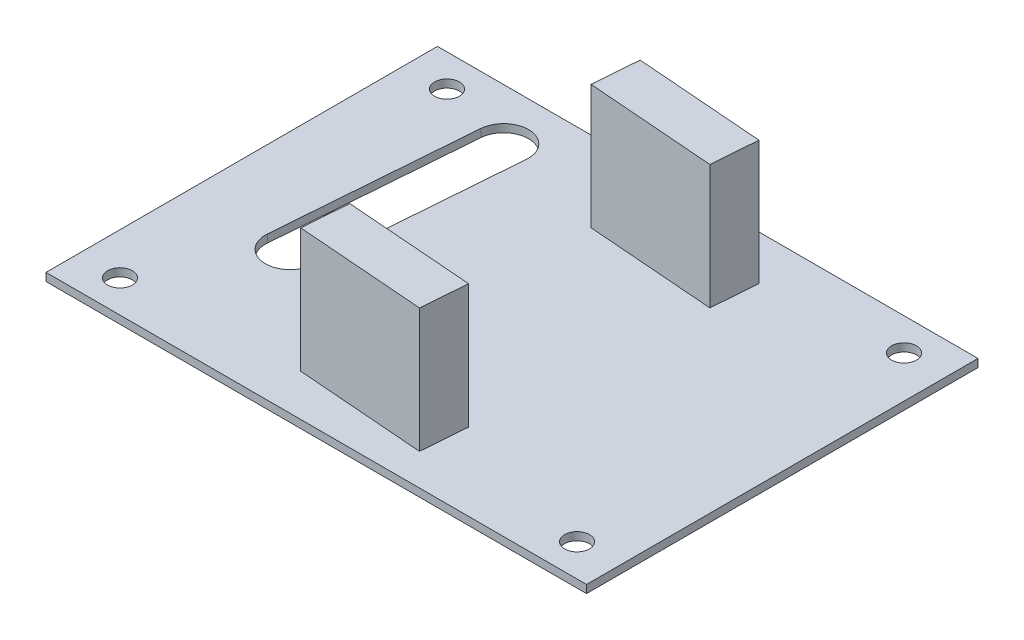
SolidWorks part; units mm, degrees
ref_plane "Ön Düzlem" through (0, 0, 0) normal (0, 0, 1) x (1, 0, 0)
ref_plane "Üst Düzlem" through (0, 0, 0) normal (0, 1, 0) x (1, 0, 0)
ref_plane "Sağ Düzlem" through (0, 0, 0) normal (1, 0, 0) x (0, 0, -1)
sketch "Çizim1" plane through (0, 0, 0) normal (0, 1, 0) x (1, 0, 0)
  line L1 (0, 0) -> (54.4, 0)
  line L2 (0, 0) -> (0, 39.4)
  line L3 (0, 39.4) -> (54.4, 39.4)
  line L4 (54.4, 0) -> (54.4, 39.4)
  dimension "D1" = 54.4
  dimension "D2" = 39.4
extrude "Yükseklik-Ekstrüzyon1" add sketch "Çizim1" along normal blind 0.8
sketch "Çizim2" plane through (0, 0.8, 0) normal (0, 1, 0) x (1, 0, 0)
  line L0 (4.2, 3.2455) -> (50.2, 36.1545) construction
  line L1 (4.2, 36.1545) -> (50.2, 3.2455) construction
  line L2 (27.2, 39.4) -> (27.2, 0) construction
  line L3 (54.4, 39.4) -> (0, 39.4) construction
  line L4 (0, 0) -> (54.4, 0) construction
  circle A4 centre (4.2, 36.1545) radius 1.25
  circle A5 centre (50.2, 36.1545) radius 1.25
  circle A6 centre (4.2, 3.2455) radius 1.25
  circle A7 centre (50.2, 3.2455) radius 1.25
  point P10 (27.2, 19.7)
  point P14 (0, 0)
  dimension "D1" = 46
  dimension "D3" = 2.5
  dimension "D2" = 32.9091
extrude "Kes-Ekstrüzyon1" cut sketch "Çizim2" against normal through all
sketch "Çizim3" plane through (0, 0.8, 0) normal (0, 1, 0) x (1, 0, 0)
  line L0 (0, 0) -> (54.4, 39.4) construction
  line L1 (12.0303, 36.8258) -> (9.5685, 5.1212) construction
  line L2 (12.0303, 36.8258) -> (44.8315, 34.2788) construction
  line L3 (9.5685, 5.1212) -> (42.3697, 2.5742) construction
  line L4 (44.8315, 34.2788) -> (42.3697, 2.5742) construction
  line L6 (43.6006, 18.4265) -> (10.7994, 20.9735) construction
  line L7 (0, 0) -> (54.4, 0) construction
  line L8 (44.8315, 34.2788) -> (44.4754, 29.6926)
  line L9 (44.8315, 34.2788) -> (23.8946, 35.9045)
  line L10 (44.4754, 29.6926) -> (23.5384, 31.3183)
  line L11 (23.8946, 35.9045) -> (23.5384, 31.3183)
  line L12 (42.3697, 2.5742) -> (42.7258, 7.1604)
  line L13 (42.3697, 2.5742) -> (21.4328, 4.2)
  line L14 (42.7258, 7.1604) -> (21.7889, 8.7862)
  line L15 (21.4328, 4.2) -> (21.7889, 8.7862)
  line L16 (34.3937, 3.1936) -> (34.7499, 7.7798)
  line L17 (36.4994, 30.3119) -> (36.8555, 34.8981)
  line L18 (10.2807, 14.2936) -> (11.829, 34.2336) construction
  line L19 (7.7882, 14.4871) -> (9.3365, 34.4271)
  line L20 (12.7732, 14.1) -> (14.3215, 34.04)
  arc A0 (7.7882, 14.4871) -> (12.7732, 14.1) centre (10.2807, 14.2936) ccw
  arc A1 (14.3215, 34.04) -> (9.3365, 34.4271) centre (11.829, 34.2336) ccw
  point P4 (27.2, 19.7)
  point P25 (11.0548, 24.2636)
  point P30 (17.7833, 28.8821)
  point P31 (16.4796, 32.0449)
  point P32 (0, 0)
  point P33 (11.2528, 26.8134)
  point P34 (11.6026, 31.3183)
  point P35 (0, 0)
  point P36 (10.304, 14.5933)
  dimension "D1" = 4.44
  dimension "D2" = 32.9
  dimension "D3" = 31.8
  dimension "D4" = 22.6
  dimension "D5" = 21
  dimension "D6" = 8
  dimension "D7" = 5
  dimension "D8" = 20
  dimension "D9" = 8
extrude "Yükseklik-Ekstrüzyon2" add sketch "Çizim3" along normal blind 12.5 contours L10 L17 L9 L11 | L13 L16 L14 L15 region at (30.197, 0.8, -33.1082) region at (28.0913, 0.8, -5.9899)
extrude "Kes-Ekstrüzyon2" cut sketch "Çizim3<3>" against normal through all contours L20 A1 L19 A0 region at (11.0548, 0.8, -24.2636)
sketch "Çizim3<3>" plane through (0, 0.8, 0) normal (0, 1, 0) x (1, 0, 0) same geometry as "Çizim3"
